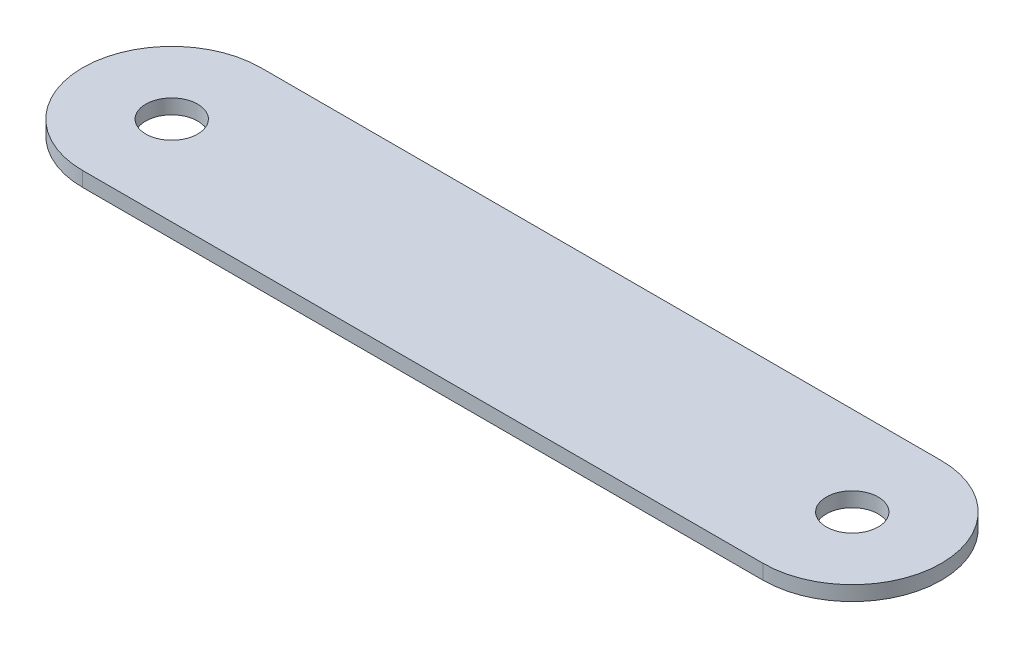
SolidWorks part; units mm, degrees
ref_plane "Front" through (0, 0, 0) normal (0, 0, 1) x (1, 0, 0)
ref_plane "Top" through (0, 0, 0) normal (0, 1, 0) x (1, 0, 0)
ref_plane "Right" through (0, 0, 0) normal (1, 0, 0) x (0, 0, -1)
sketch "Sketch1" plane through (0, 0, 0) normal (0, 1, 0) x (1, 0, 0)
  line L0 (-69.5, 0) -> (69.5, 0) construction
  line L1 (-69.5, 18.193) -> (69.5, 18.193)
  line L2 (-69.5, -18.193) -> (69.5, -18.193)
  arc A0 (-69.5, 18.193) -> (-69.5, -18.193) centre (-69.5, 0) ccw
  arc A1 (69.5, -18.193) -> (69.5, 18.193) centre (69.5, 0) ccw
  circle A2 centre (-69.5, 0) radius 5.3
  circle A4 centre (69.5, 0) radius 5.3
  point P2 (69.5, 0)
  point P3 (0, 0)
  dimension "D1" = 10.6
  dimension "D2" = 18.193
  dimension "D4" = 10.6
  dimension "D3" = 139
extrude "Boss-Extrude1" add sketch "Sketch1" along normal blind 3
